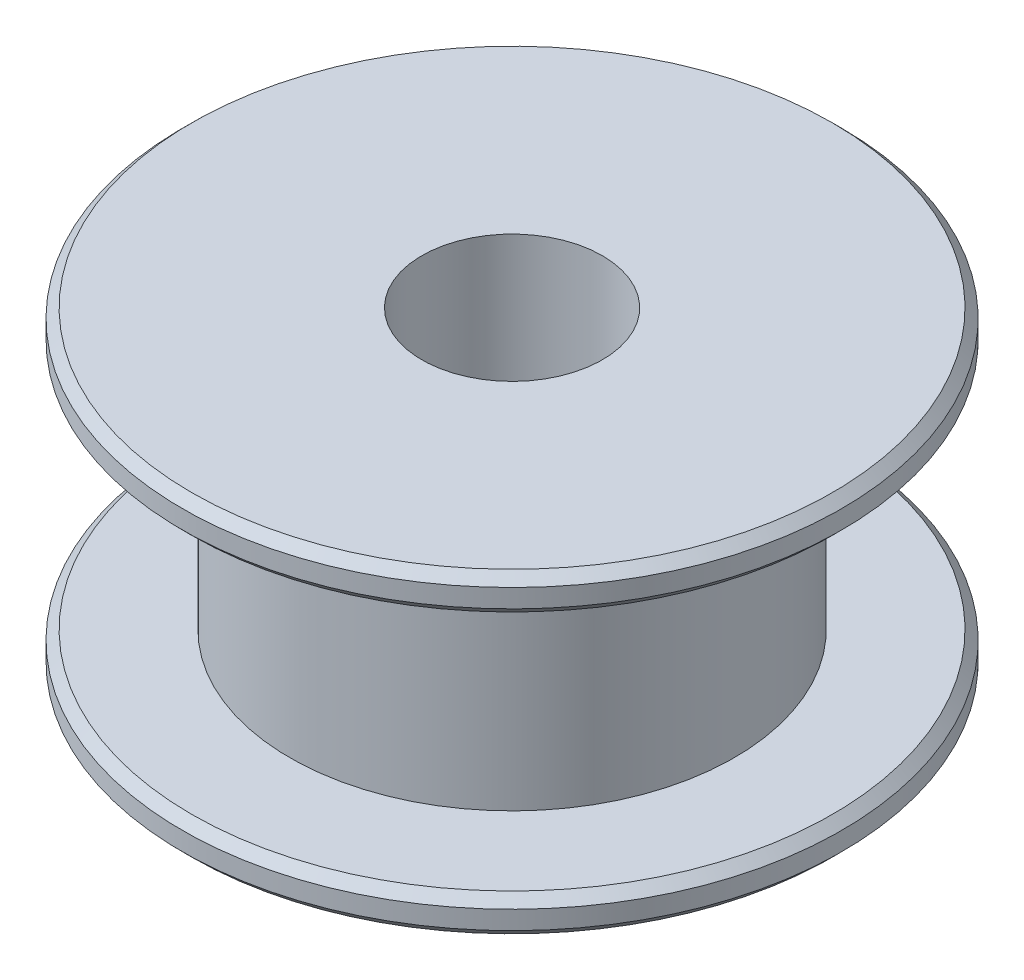
SolidWorks part; units mm, degrees
ref_plane "Front Plane" through (0, 0, 0) normal (0, 0, 1) x (1, 0, 0)
ref_plane "Top Plane" through (0, 0, 0) normal (0, 1, 0) x (1, 0, 0)
ref_plane "Right Plane" through (0, 0, 0) normal (1, 0, 0) x (0, 0, -1)
sketch "Sketch1" plane through (0, 0, 0) normal (0, 0, 1) x (1, 0, 0)
  line L0 (2.4765, 8.6614) -> (2.4765, 0)
  line L1 (2.4765, 0) -> (8.7884, 0)
  line L2 (8.7884, 0) -> (9.0424, 0.254)
  line L3 (9.0424, 0.254) -> (9.0424, 0.762)
  line L4 (9.0424, 0.762) -> (8.7884, 1.016)
  line L5 (8.7884, 1.016) -> (6.096, 1.016)
  line L6 (6.096, 1.016) -> (6.096, 7.6454)
  line L7 (6.096, 7.6454) -> (8.7884, 7.6454)
  line L8 (8.7884, 7.6454) -> (9.0424, 7.8994)
  line L9 (9.0424, 7.8994) -> (9.0424, 8.4074)
  line L10 (9.0424, 8.4074) -> (8.7884, 8.6614)
  line L11 (8.7884, 8.6614) -> (2.4765, 8.6614)
  line L12 (0, 8.6614) -> (0, 0) construction
revolve "Revolve1" add sketch "Sketch1" angle 360 about L12 reverse direction yes
